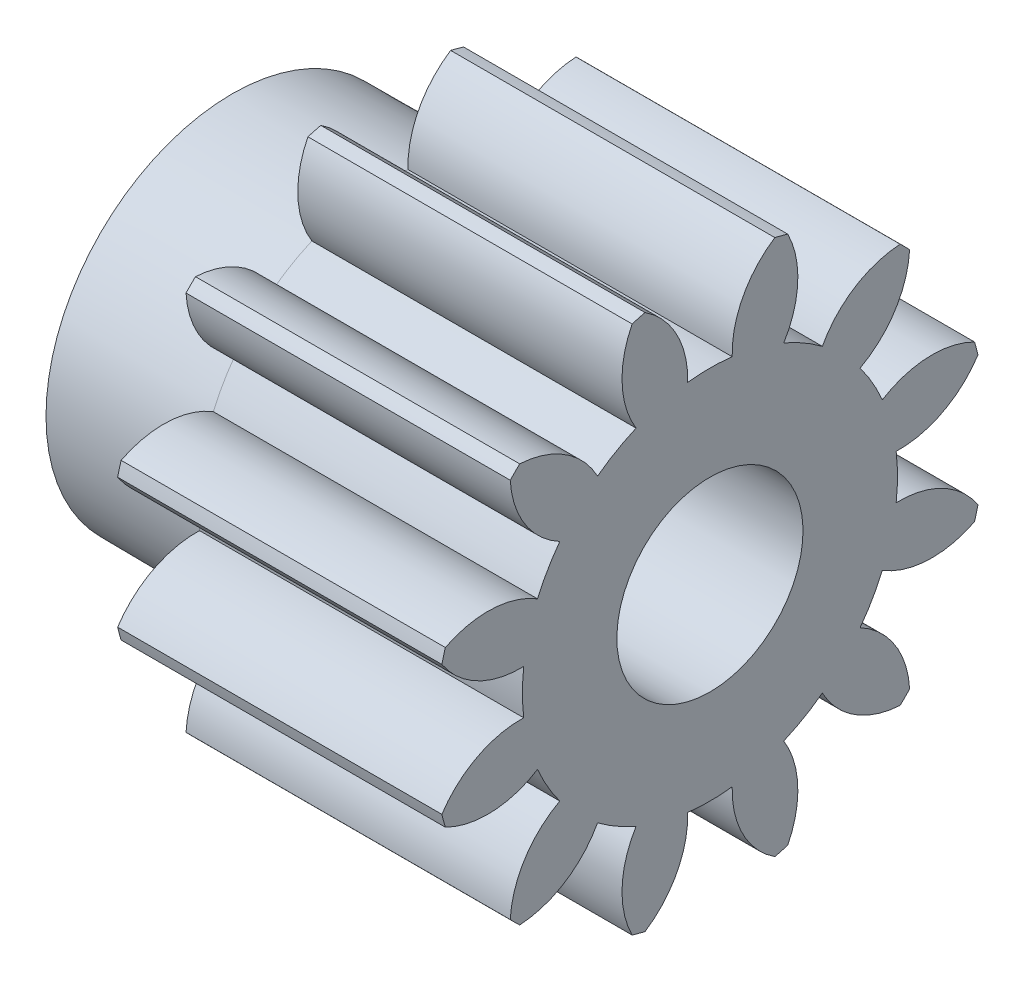
SolidWorks part; units mm, degrees
ref_plane "Plane1" through (0, 0, 0) normal (0, 0, 1) x (1, 0, 0)
ref_plane "Plane2" through (0, 0, 0) normal (0, 1, 0) x (1, 0, 0)
ref_plane "Plane3" through (0, 0, 0) normal (1, 0, 0) x (0, 0, -1)
sketch "HoldingSke" plane through (0, 0, 0) normal (0, 1, 0) x (1, 0, 0)
  line L0 (0, 0) -> (496.899, -105.6191)
  line L1 (-15, 0) -> (100, 0) construction
  line L2 (0, 0) -> (-2.1039, 2.3779)
  line L3 (0, 0) -> (-11.863, 4.5341)
  line L4 (0, 0) -> (8.4473, 1.7955)
  line L5 (0, 0) -> (-47.5972, -17.7524)
  line L6 (0, 0) -> (-10.5278, -7.1032)
  line L7 (-2.1039, 2.3779) -> (8.8308, 51.9871)
  line L8 (-76.2, 54.61) -> (-69.596, 54.61)
  line L9 (-71.009, 38.7566) -> (-53.1078, 45.2721)
  line L10 (-76.2, 71.12) -> (104.1128, 71.12)
  line L11 (0, 0) -> (-12.7, 0)
  line L12 (-76.2, 101.6) -> (-76.1492, 101.6)
  line L13 (24.9733, 27.94) -> (52.9518, 28.4284)
  line L14 (24.9733, 27.94) -> (25.0241, 27.9398)
  line L15 (24.9733, 27.94) -> (100.4021, 29.52)
  circle A0 centre (0, 0) radius 3.175
  circle A1 centre (0, 0) radius 6.0452
  circle A2 centre (0, 0) radius 38.1
  circle A3 centre (0, 0) radius 3.175
  dimension "Num_teeth" = 12
  dimension "H" = 19.05
  dimension "Pitch_radius" = 180.3128
  dimension "Width" = 12.7
  dimension "Thickness" = 12.7
sketch "BasProSke" plane through (0, 0, 0) normal (0, 1, 0) x (1, 0, 0)
  line L0 (-10, 0) -> (60, 0) construction
  line L1 (0, 0) -> (0, 8.89)
  line L2 (0, 0) -> (12.7, 0)
  line L3 (12.7, 0) -> (12.7, 8.89)
  line L4 (12.7, 8.89) -> (0, 8.89)
  dimension "Thickness" = 12.7
  dimension "Diameter" = 17.78
revolve "Base-Revolve" add sketch "BasProSke" angle 360 about L0
sketch "TooCutSke" plane through (0, 0, 0) normal (1, 0, 0) x (0, 0, -1)
  line L1 (0, 0) -> (0, 107) construction
  line L2 (0, 0) -> (-1.0834, 7.5426) construction
  line L3 (0, 0) -> (-3.9164, 14.6164) construction
  line L4 (-1.0834, 7.5426) -> (-1.9582, 7.3082) construction
  arc A0 (0.7171, 6.0025) -> (-0.7171, 6.0025) centre (0, 0) ccw
  arc A1 (2.1216, 8.6593) -> (-2.1216, 8.6593) centre (0, 0) ccw
  circle A2 centre (0, 0) radius 7.62 construction
  circle A3 centre (0, 0) radius 7.1605 construction
  arc A4 (-0.7171, 6.0025) -> (-2.1216, 8.6593) centre (-3.7638, 6.0915) ccw
  arc A5 (2.1216, 8.6593) -> (0.7171, 6.0025) centre (3.7638, 6.0915) ccw
extrude "ToothCut" cut sketch "TooCutSke" along normal through all
fillet "Breaks" [suppressed] radius 0.0254 tangent propagation no
fillet "RootFillets" [suppressed] radius 0.3048
pattern_circular "TeethCuts" count 12 every 30 about axis through (-10, 0, 0) along (1, 0, 0) of "ToothCut", "RootFillets", "Breaks"
sketch "HubNeaOneSke" plane through (0, 0, 0) normal (-1, 0, 0) x (0, 0, 1)
  circle A0 centre (0, 0) radius 6.0452
  dimension "Diameter" = 12.0904
extrude "HubNearOne" [suppressed] add sketch "HubNeaOneSke" along normal blind 38.1001
sketch "HubNeaBotSke" plane through (0, 0, 0) normal (-1, 0, 0) x (0, 0, 1)
  circle A0 centre (0, 0) radius 6.0452
  dimension "Diameter" = 12.0904
extrude "HubNearBoth" [suppressed] add sketch "HubNeaBotSke" along normal blind 19.05
ref_plane "FarPln" through (12.7, 0, 0) normal (1, 0, 0) x (0, 0, -1)
sketch "HubFarSke" plane through (12.7, 0, 0) normal (1, 0, 0) x (0, 0, -1)
  circle A0 centre (0, 0) radius 6.0452
  dimension "Diameter" = 12.0904
extrude "HubFar" [suppressed] add sketch "HubFarSke" along normal blind 19.05
sketch "BorSke" plane through (0, 0, 0) normal (1, 0, 0) x (0, 0, -1)
  circle A0 centre (0, 0) radius 3
  dimension "D1" = 6
extrude "Bore" cut sketch "BorSke" along normal mid plane 101.6001
sketch "KeySke" plane through (0, 0, 0) normal (1, 0, 0) x (0, 0, -1)
  line L0 (-0.127, 0) -> (-0.127, 3.429)
  line L1 (-0.127, 3.429) -> (0.127, 3.429)
  line L2 (0.127, 3.429) -> (0.127, 0)
  line L3 (0, 0) -> (0, 34) construction
  line L4 (-0.127, 0) -> (0.127, 0)
  dimension "Width" = 0.254
extrude "Keyway" [suppressed] cut sketch "KeySke" along normal mid plane 101.6001
pattern_circular "Keyway2" [suppressed] count 2 every 90 about axis through (-10, 0, 0) along (1, 0, 0) reverse direction yes
sketch "Sketch1" plane through (0, 0, 0) normal (0, 0, 1) x (1, 0, 0)
  line L0 (0, 0) -> (-2.5422, 0) construction
  line L1 (0, -4) -> (-4.95, -4)
  line L2 (-4.95, -4) -> (-4.95, -6)
  line L3 (-4.95, -6) -> (0, -6.0452)
  line L4 (0, -6.0452) -> (0, -4)
  dimension "D1" = 2
  dimension "D2" = 4
  dimension "D3" = 4.95
revolve "Revolve1" add sketch "Sketch1" angle 360 about L0
sketch "Sketch2" plane through (0, 0, 0) normal (0, 0, 1) x (1, 0, 0)
  line L0 (12.7, -8.6403) -> (0, -8.6403) construction
  line L1 (12.7, 8.6403) -> (10.45, 8.6403)
  line L2 (12.7, 8.6403) -> (12.7, -8.6403)
  line L3 (12.7, -8.6403) -> (10.45, -8.6403)
  line L4 (10.45, 8.6403) -> (10.45, -8.6403)
  dimension "D1" = 2.25
extrude "Cut-Extrude1" cut sketch "Sketch2" against normal through all both and the other way through all
ref_axis "Axis1" through (-4.95, 0, 0) along (1, 0, 0)
equation "' \"Pitch@HoldingSke\" = 4"
equation "' \"Num_teeth@HoldingSke\" = 12"
equation "' \"Ap@HoldingSke\" =  20"
equation "' \"Ap@HoldingSke\" = 20"
equation "' \"Width@HoldingSke\" = 0.5"
equation "' \"Hub_dia@HoldingSke\"= 1"
equation "' \"Hub_dia@HoldingSke\" = 1"
equation "' \"Overall_len@HoldingSke\" = 1.0"
equation "' \"Bore@HoldingSke\" = 0.75"
equation "' \"T_dim@HoldingSke\" = 0.85"
equation "' \"Width@KeySke\" = 0.25"
equation "' \"Show_teeth@HoldingSke\" = 13"
equation "' \"Backlash@HoldingSke\" = 0.009"
equation "' \"Addendum_fac@HoldingSke\" = 1.0"
equation "' \"Dedendum_fac@HoldingSke\" = 1.25"
equation "' \"Dedendum_add@HoldingSke\" = 0.00005"
equation "' \"Clearance_fac@HoldingSke\" = 0.25"
equation "' \"Pitch@HoldingSke\" = 0.5"
equation "' \"Num_teeth@HoldingSke\" = 23"
equation "' \"Show_teeth@HoldingSke\" = 23"
equation "' \"Backlash@HoldingSke\" = 0.0375"
equation "\"Overcut_dia@TooCutSke\" = (\"Num_teeth@HoldingSke\" + 2 * \"Addendum_fac@HoldingSke\") / \"Pitch@HoldingSke\" + 0.002"
equation "\"Pitch_dia@TooCutSke\" = \"Num_teeth@HoldingSke\" / \"Pitch@HoldingSke\""
equation "\"Base_dia@TooCutSke\" = \"Num_teeth@HoldingSke\" / \"Pitch@HoldingSke\" * cos((\"Ap@HoldingSke\"  * 3.14159265 / 180))"
equation "\"Root_dia@TooCutSke\" = (\"Num_teeth@HoldingSke\" + 2) / \"Pitch@HoldingSke\" - 2 * (\"Addendum_fac@HoldingSke\" + \"Dedendum_fac@HoldingSke\") / \"Pitch@HoldingSke\" - \"Dedendum_add@HoldingSke\" * 2"
equation "\"Half_ang@TooCutSke\" = 180 / \"Num_teeth@HoldingSke\""
equation "\"Half_CT@TooCutSke\" = \"Num_teeth@HoldingSke\" / \"Pitch@HoldingSke\" * sin((3.14159265 / 2 / \"Num_teeth@HoldingSke\")) / 2 - 7 * \"Backlash@HoldingSke\" / 4"
equation "\"Flank_rad@TooCutSke\" = \"Num_teeth@HoldingSke\" / \"Pitch@HoldingSke\" / 5"
equation "\"Radius@RootFillets\" = \"Clearance_fac@HoldingSke\" / \"Pitch@HoldingSke\" + \"Dedendum_add@HoldingSke\""
equation "\"Break_rad@Breaks\" = 0.02 / \"Pitch@HoldingSke\""
equation "\"Thickness@HoldingSke\" = \"Width@HoldingSke\""
equation "\"OAL@HoldingSke\" = \"Thickness@HoldingSke\""
equation "\"MHD@HoldingSke\" = (\"Num_teeth@HoldingSke\" + 2) / \"Pitch@HoldingSke\" - 2 * (\"Addendum_fac@HoldingSke\" + \"Dedendum_fac@HoldingSke\")  / \"Pitch@HoldingSke\" - \"Dedendum_add@HoldingSke\" * 2"
equation "\"MBD@HoldingSke\" = (\"Num_teeth@HoldingSke\" + 2) / \"Pitch@HoldingSke\" - 2 * (\"Addendum_fac@HoldingSke\" + \"Dedendum_fac@HoldingSke\")  / \"Pitch@HoldingSke\" - \"Dedendum_add@HoldingSke\" * 2 - 0.002"
equation "\"MHD@HoldingSke\" = ((sgn( \"MHD@HoldingSke\" - \"Hub_dia@HoldingSke\" )-1)*( \"MHD@HoldingSke\" - \"Hub_dia@HoldingSke\" ))/-2+ \"Hub_dia@HoldingSke\""
equation "\"MBD@HoldingSke\" = ((sgn( \"MBD@HoldingSke\" - \"Bore@HoldingSke\" )-1)*( \"MBD@HoldingSke\" - \"Bore@HoldingSke\" ))/-2+ \"Bore@HoldingSke\""
equation "\"OAL@HoldingSke\" = ((sgn( \"OAL@HoldingSke\" - \"Overall_len@HoldingSke\" )+1)*( \"OAL@HoldingSke\" - \"Overall_len@HoldingSke\" ))/2 + \"Overall_len@HoldingSke\" + 0.000002"
equation "\"Num_teeth@TeethCuts\" = int( \"Show_teeth@HoldingSke\" ) + 1"
equation "\"Num_teeth@TeethCuts\" = ((sgn( \"Num_teeth@TeethCuts\" - \"Num_teeth@HoldingSke\" )-1)*( \"Num_teeth@TeethCuts\" - \"Num_teeth@HoldingSke\" ))/-2+ \"Num_teeth@HoldingSke\""
equation "\"Num_teeth@TeethCuts\" = ((sgn( \"Num_teeth@TeethCuts\" - 2.0)+1)*( \"Num_teeth@TeethCuts\" - 2.0))/2 +2.0"
equation "\"Angle@TeethCuts\" = 360.0 / \"Num_teeth@HoldingSke\""
equation "\"Diameter@BasProSke\" = (\"Num_teeth@HoldingSke\" + 2 * \"Addendum_fac@HoldingSke\") / \"Pitch@HoldingSke\""
equation "\"Thickness@BasProSke\"  = \"Thickness@HoldingSke\""
equation "' \"Fillet_rad@BasProSke\" =  \"Thickness@HoldingSke\" * 0.05"
equation "' \"Fillet_rad@BasProSke\" = \"Thickness@HoldingSke\" * 0.05"
equation "\"MHD@HoldingSke\" = ((sgn( \"MHD@HoldingSke\" - \"Root_dia@TooCutSke\" )-1)*( \"MHD@HoldingSke\" - \"Root_dia@TooCutSke\" ))/-2+ \"Root_dia@TooCutSke\""
equation "\"Diameter@HubNeaOneSke\" = \"MHD@HoldingSke\""
equation "\"Length@HubNearOne\" = \"OAL@HoldingSke\" - \"Thickness@BasProSke\""
equation "\"Diameter@HubNeaBotSke\" = \"MHD@HoldingSke\""
equation "\"Length@HubNearBoth\" = ( \"OAL@HoldingSke\" - \"Thickness@BasProSke\" ) / 2.0"
equation "\"Thickness@FarPln\" = \"Thickness@BasProSke\""
equation "\"Diameter@HubFarSke\" = \"MHD@HoldingSke\""
equation "\"Length@HubFar\" = ( \"OAL@HoldingSke\" - \"Thickness@BasProSke\" ) / 2.0"
equation "\"D1@Bore\" = \"OAL@HoldingSke\" * 2.0"
equation "\"D1@Keyway\" = \"OAL@HoldingSke\" * 2.0"
equation "\"Offset@KeySke\" = \"T_dim@HoldingSke\" - \"MBD@HoldingSke\" / 2.0"
